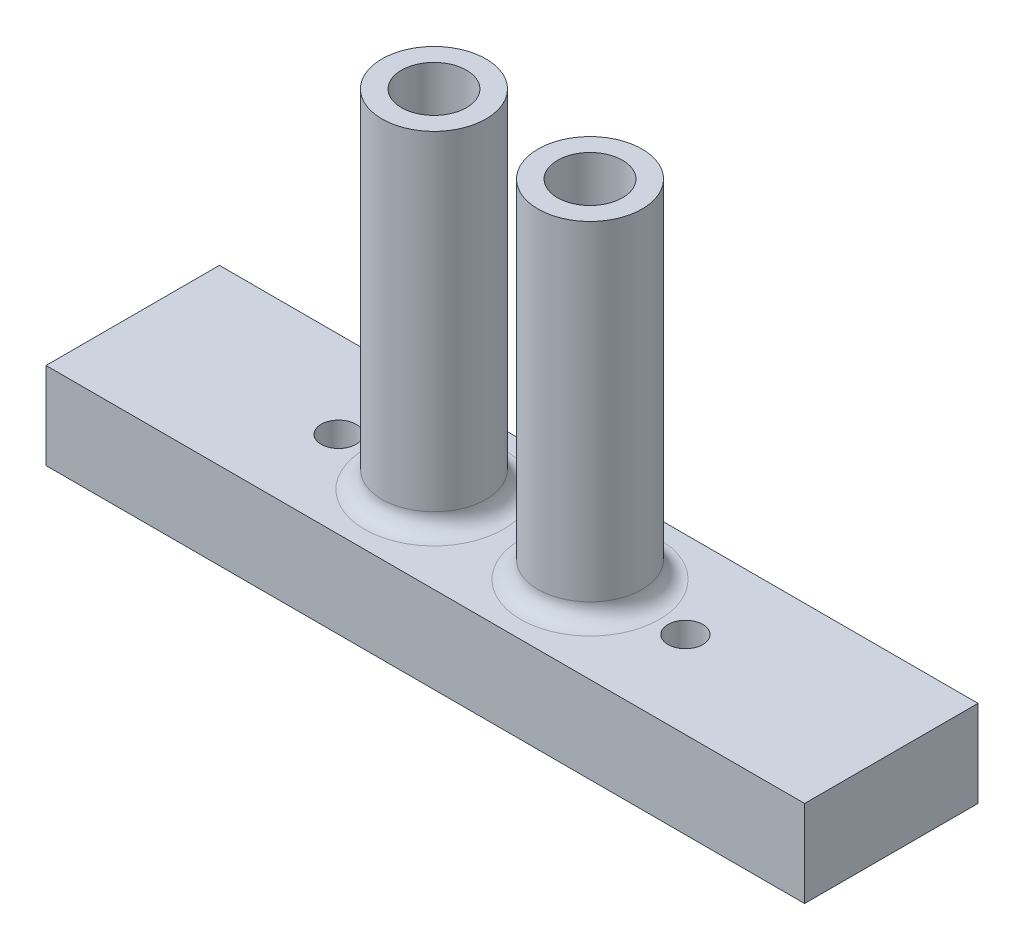
SolidWorks part; units mm, degrees
ref_plane "Front Plane" through (0, 0, 0) normal (0, 0, 1) x (1, 0, 0)
ref_plane "Top Plane" through (0, 0, 0) normal (0, 1, 0) x (1, 0, 0)
ref_plane "Right Plane" through (0, 0, 0) normal (1, 0, 0) x (0, 0, -1)
sketch "Sketch1" plane through (0, 0, 0) normal (0, 1, 0) x (1, 0, 0)
  line L1 (0, 0) -> (-111.125, 0)
  line L2 (0, 0) -> (0, -25.4)
  line L3 (0, -25.4) -> (-111.125, -25.4)
  line L4 (-111.125, 0) -> (-111.125, -25.4)
  dimension "D1" = 111.125
  dimension "D2" = 25.4
extrude "Boss-Extrude1" add sketch "Sketch1" along normal blind 12.7 contours L2 L1 L4 L3
sketch "Sketch2" plane through (0, 12.7, 0) normal (0, 1, 0) x (1, 0, 0)
  line L1 (0, 0) -> (0, -25.4) construction
  line L3 (0, -25.4) -> (-111.125, -25.4) construction
  line L4 (0, 0) -> (-111.125, 0) construction
  circle A1 centre (-30.1625, -12.7) radius 2.5527
  circle A2 centre (-80.9625, -12.7) radius 2.5527
  circle A3 centre (-66.9925, -12.7) radius 9.525 construction
  circle A4 centre (-44.1325, -12.7) radius 9.525 construction
  circle A5 centre (-44.1325, -12.7) radius 7.62
  circle A6 centre (-66.9925, -12.7) radius 7.62
  circle A8 centre (-44.1325, -12.7) radius 4.7625
  circle A9 centre (-66.9925, -12.7) radius 4.7625
  point P17 (-55.5625, -25.4)
  point P23 (0, -12.7)
  dimension "D1" = 15.24
  dimension "D3" = 12.7
  dimension "D2" = 15.24
  dimension "D4" = 12.7
  dimension "D5" = 11.43
  dimension "D6" = 11.43
extrude "Boss-Extrude2" add sketch "Sketch2" along normal blind 50.8 contours A8 | A5 | A9 | A6
extrude "Cut-Extrude1" cut sketch "Sketch2<9>" against normal through all contours A1 | A2
sketch "Sketch2<9>" plane through (0, 12.7, 0) normal (0, 1, 0) x (1, 0, 0) same geometry as "Sketch2"
fillet "Fillet1" radius 2.54 2 edges at (-44.1325, 12.7, 20.32) (-66.9925, 12.7, 20.32)
